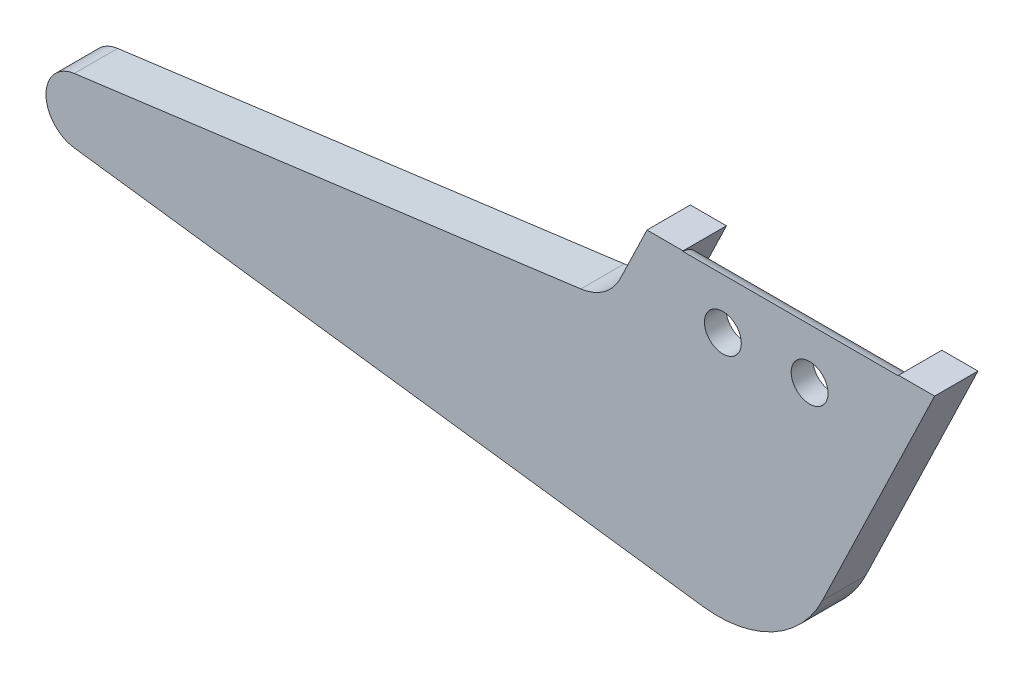
SolidWorks part; units mm, degrees
ref_plane "Front Plane" through (0, 0, 0) normal (0, 0, 1) x (1, 0, 0)
ref_plane "Top Plane" through (0, 0, 0) normal (0, 1, 0) x (1, 0, 0)
ref_plane "Right Plane" through (0, 0, 0) normal (1, 0, 0) x (0, 0, -1)
sketch "Esquisse1" plane through (0, 0, 0) normal (0, 0, 1) x (1, 0, 0)
  line L0 (16.3308, 16.8755) -> (6.6619, -3.2074) construction
  line L1 (6.6619, -3.2074) -> (15.5123, 15.1755) construction
  line L2 (-2.8692, 16.8755) -> (-6.0284, 10.3137) construction
  line L3 (-3.6877, 15.1755) -> (-6.0284, 10.3137) construction
  line L4 (16.3308, 16.8755) -> (-2.8692, 16.8755) construction
  line L5 (-12.1923, 5.8525) -> (-56.6463, 0) construction
  line L6 (-0.9651, -7.3306) -> (-56.6463, 0) construction
  line L7 (-51.5464, -0.6714) -> (0.2611, -7.492) construction
  line L8 (-51.5464, 0.6714) -> (-12.1923, 5.8525) construction
  line L9 (15.5123, 15.1755) -> (-3.6877, 15.1755) construction
  line L10 (-3.2022, 16.8755) -> (-6.2987, 10.4439)
  line L11 (-12.2314, 6.1499) -> (-51.4139, 0.9914)
  line L12 (-1.0042, -7.628) -> (-51.4139, -0.9914)
  line L13 (16.6637, 16.8755) -> (6.9322, -3.3375)
  line L14 (-6.5318, 16.8755) -> (-9.0017, 11.7452)
  line L15 (-12.623, 9.1242) -> (-59.3363, 2.9743)
  line L16 (-1.3958, -10.6023) -> (-59.3363, -2.9743)
  line L17 (19.9933, 16.8755) -> (9.6353, -4.6389)
  line L18 (19.9933, 16.8755) -> (-6.5318, 16.8755)
  line L19 (-5.8426, 18.307) -> (-9.0017, 11.7452) construction
  line L20 (-3.1395, 17.0057) -> (-6.2987, 10.4439) construction
  line L21 (16.6011, 16.7454) -> (6.9322, -3.3375) construction
  line L22 (19.3041, 15.444) -> (9.6353, -4.6389) construction
  line L23 (-12.2314, 6.1499) -> (-58.9447, 0) construction
  line L24 (-1.0042, -7.628) -> (-58.9447, 0) construction
  line L25 (-12.623, 9.1242) -> (-81.9286, 0) construction
  line L26 (-1.3958, -10.6023) -> (-81.9286, 0) construction
  arc A0 (-6.0284, 10.3137) -> (-12.1923, 5.8525) centre (-13.2365, 13.784) cw construction
  arc A1 (-6.2987, 10.4439) -> (-12.2314, 6.1499) centre (-13.2365, 13.784) cw
  circle A2 centre (0.468, 12.1755) radius 1.7 construction
  circle A3 centre (8.468, 12.1755) radius 1.7
  circle A4 centre (0.468, 12.1755) radius 1.7
  circle A5 centre (8.468, 12.1755) radius 1.7 construction
  arc A6 (6.6619, -3.2074) -> (-0.9651, -7.3306) centre (0, 0) cw construction
  arc A7 (6.9322, -3.3375) -> (-1.0042, -7.628) centre (0, 0) cw
  arc A8 (-9.0017, 11.7452) -> (-12.623, 9.1242) centre (-13.2365, 13.784) cw
  arc A9 (9.6353, -4.6389) -> (-1.3958, -10.6023) centre (0, 0) cw
  arc A10 (-51.4139, 0.9914) -> (-51.4139, -0.9914) centre (-51.2834, 0) ccw
  arc A11 (-59.3363, 2.9743) -> (-59.3363, -2.9743) centre (-58.9447, 0) ccw
  point P52 (16.8929, 16.8755)
  point P53 (0, 0)
  point P54 (0, 0)
  point P55 (-6.7547, 16.8755)
  point P57 (-3.4258, 16.8755)
  point P59 (0, 0)
  point P60 (-6.8419, 16.8755)
  point P62 (20.7591, 18.005)
  point P64 (21.041, 16.8755)
  point P65 (20.2193, 16.8755)
  point P66 (20.323, 16.8755)
  dimension "D4" = 1
  dimension "D5" = 3
  dimension "D1" = 3
  dimension "D2" = 0.3
  dimension "D3" = 3
extrude "Boss.-Extru.1" add sketch "Esquisse1" along normal blind 2 contours L15 A11 L16 A9 L17 L18 L13 A7 L12 A10 L11 A1 L10 L14 A8 | L11 A10 L12 A7 L13 L18 L10 A1 A3 A4 region at (-9.8414, 2.9886, 0) region at (-5.5294, 14.0347, 0)
extrude "Boss.-Extru.2" add sketch "Esquisse1<5>" against normal blind 2 contours L15 A11 L16 A9 L17 L18 L13 A7 L12 A10 L11 A1 L10 L14 A8 region at (-5.5294, 14.0347, 0)
sketch "Esquisse1<5>" plane through (0, 0, 0) normal (0, 0, 1) x (1, 0, 0) same geometry as "Esquisse1"
fillet "Congé1" radius 2.5 1 edges at (6.7308, 16.8755, 0)
